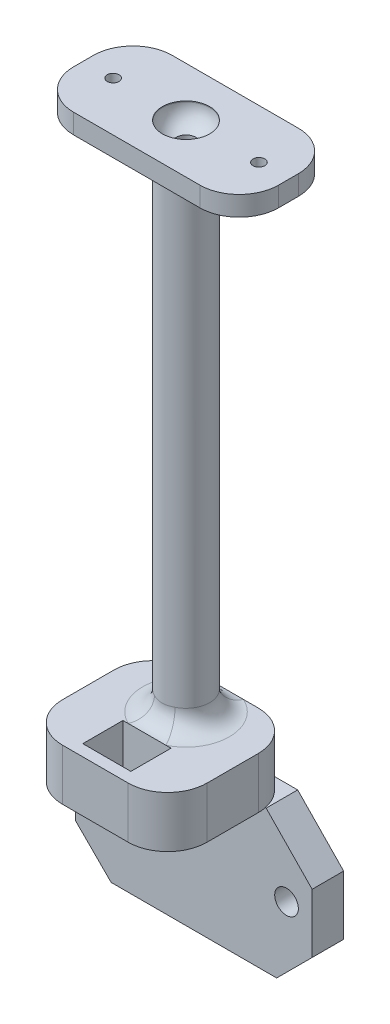
SolidWorks part; units mm, degrees
ref_plane "前视基准面" through (0, 0, 0) normal (0, 0, 1) x (1, 0, 0)
ref_plane "上视基准面" through (0, 0, 0) normal (0, 1, 0) x (1, 0, 0)
ref_plane "右视基准面" through (0, 0, 0) normal (1, 0, 0) x (0, 0, -1)
sketch "草图1" plane through (0, 0, 0) normal (0, 1, 0) x (1, 0, 0)
  line L0 (-32.0093, 0) -> (32.0093, 0) construction
  line L1 (-26, 12.5) -> (26, 12.5)
  line L2 (-26, 12.5) -> (-26, -12.5)
  line L3 (-26, -12.5) -> (26, -12.5)
  line L4 (26, 12.5) -> (26, -12.5)
  line L5 (-26, 12.5) -> (26, -12.5) construction
  line L6 (-26, -12.5) -> (26, 12.5) construction
  line L7 (0, 19.5739) -> (0, -19.5739) construction
  circle A0 centre (-18.5, 0) radius 1.5
  circle A1 centre (18.5, 0) radius 1.5
  point P0 (0, 0)
  point P9 (0, 0)
  point P12 (0, 0)
  dimension "D4" = 3
  dimension "D1" = 52
  dimension "D2" = 25
  dimension "D3" = 37
extrude "凸台-拉伸1" add sketch "草图1" along normal blind 5
sketch "草图2" plane through (0, 0, 0) normal (0, -1, 0) x (1, 0, 0)
  circle A0 centre (0, 0) radius 4
  circle A1 centre (0, 0) radius 2.5
  circle A2 centre (0, 0) radius 6
  dimension "D1" = 8
  dimension "D2" = 5
  dimension "D3" = 12
extrude "凸台-拉伸2" add sketch "草图2" along normal blind 125 contours A0 A1 region at (-3.8869, 0, 0)
fillet "圆角1" radius 10 4 edges at (26, 2.5, -12.5) (26, 2.5, 12.5) (-26, 2.5, -12.5) (-26, 2.5, 12.5)
extrude "凸台-拉伸4" add sketch "草图2<3>" along normal up to surface (125 mm away) contours A2 A0 region at (-5.8303, 0, 0) up to face at (0, -125, -2.5)
sketch "草图2<3>" plane through (0, 0, 0) normal (0, -1, 0) x (1, 0, 0) same geometry as "草图2"
fillet "圆角3" radius 5 1 edges at (0, 0, 6)
extrude "切除-拉伸1" cut sketch "草图2<4>" against normal blind 50 contours A2
sketch "草图2<4>" plane through (0, 0, 0) normal (0, -1, 0) x (1, 0, 0) same geometry as "草图2"
fillet "圆角4" radius 5 1 edges at (0, 0, -6)
sketch "草图3" plane through (0, 0, 0) normal (0, 0, 1) x (1, 0, 0)
  line L0 (0, -95.6549) -> (0, -154.3451) construction
  line L2 (18.3299, -125) -> (-18.3299, -125)
  line L3 (-18.3299, -125) -> (-18.3299, -138)
  line L4 (-18.3299, -138) -> (18.3299, -138)
  line L5 (18.3299, -138) -> (18.3299, -125)
  point P3 (0, -125)
  dimension "D1" = 13
extrude "凸台-拉伸5" add sketch "草图3" along normal blind 23 and the other way blind 10
sketch "草图4" plane through (0, -125, 0) normal (0, 1, 0) x (1, 0, 0)
  line L0 (0, 20.2764) -> (0, -20.2764) construction
  line L2 (-6.1, -20.1) -> (6.1, -20.1)
  line L3 (-6.1, -20.1) -> (-6.1, -9.9)
  line L4 (-6.1, -9.9) -> (6.1, -9.9)
  line L5 (6.1, -20.1) -> (6.1, -9.9)
  line L6 (-6.1, -20.1) -> (6.1, -9.9) construction
  line L7 (-6.1, -9.9) -> (6.1, -20.1) construction
  point P0 (0, -15)
  point P4 (0, 0)
  dimension "D1" = 10.2
  dimension "D2" = 12.2
  dimension "D3" = 15
extrude "切除-拉伸2" cut sketch "草图4" against normal blind 16
fillet "圆角5" radius 10 4 edges at (18.3299, -131.5, -10) (18.3299, -131.5, 23) (-18.3299, -131.5, -10) (-18.3299, -131.5, 23)
sketch "草图5" plane through (0, 0, -10) normal (0, 0, 1) x (1, 0, 0)
  line L4 (-18.3299, -138) -> (-30, -150)
  line L5 (-30, -150) -> (-30, -165)
  line L6 (-30, -165) -> (-21, -174)
  line L7 (-21, -174) -> (0, -174)
  line L8 (0, -138) -> (0, -174) construction
  line L9 (-8.3299, -138) -> (8.3299, -138) construction
  line L15 (18.3299, -138) -> (-18.3299, -138)
  line L16 (21, -174) -> (0, -174)
  line L17 (30, -165) -> (21, -174)
  line L18 (18.3299, -138) -> (30, -150)
  line L19 (30, -150) -> (30, -165)
  point P9 (-29.7731, -150)
  point P13 (-20.2959, -173)
  point P15 (0, -172.6024)
  point P17 (0.4688, -161.2707)
  dimension "D1" = 60
  dimension "D2" = 135
  dimension "D3" = 12
  dimension "D4" = 15
  dimension "D5" = 9
extrude "凸台-拉伸6" add sketch "草图5" along normal blind 8
sketch "草图6" plane through (0, -138, 0) normal (0, -1, 0) x (1, 0, 0)
  line L0 (-6.1, 20.1) -> (-6.1, 9.9) construction
  line L1 (6.1, 20.1) -> (-6.1, 20.1) construction
  line L2 (-6.1, 9.9) -> (6.1, 9.9) construction
  line L4 (6.1, 20.1) -> (-6.1, 20.1) construction
  line L6 (-6.1, 15) -> (6.1, 15) construction
  line L11 (6.1, 20.1) -> (6.1, 9.9) construction
  line L12 (-6.1, 9.9) -> (-6.1, 20.1) construction
  line L13 (1.4979, 15.0793) -> (-0.5742, 13.6143)
  line L14 (0, 20.1) -> (0, 4.7137) construction
  arc A0 (1.4979, 15.0793) -> (-0.5742, 13.6143) centre (0, 15) ccw
  dimension "D1" = 3
sketch "草图8" plane through (0, 0, -2) normal (0, 0, 1) x (1, 0, 0)
  line L0 (0, -138) -> (0, -174) construction
  line L1 (-8.3299, -138) -> (8.3299, -138) construction
  line L2 (-28.9111, -156) -> (28.9111, -156) construction
  line L4 (-21, -174) -> (21, -174) construction
  line L6 (-30, -150) -> (-30, -165) construction
  circle A0 centre (23.5, -156) radius 3
  circle A1 centre (-23.5, -156) radius 3
  point P8 (0, -156)
  point P9 (0, -175)
  point P14 (0, 0)
  point P15 (0, 0)
  point P16 (0, 0)
  point P18 (0, 0)
  point P21 (-30, -157.5)
  dimension "D1" = 6
  dimension "D2" = 47
  dimension "D3" = 1.5
sketch "草图9" plane through (0, -174, 0) normal (0, -1, 0) x (1, 0, 0)
  circle A0 centre (0, 15) radius 9
  circle A1 centre (0, 15) radius 2.5
  dimension "D1" = 18
  dimension "D2" = 5
sketch "草图10" plane through (0, -174, 0) normal (0, -1, 0) x (1, 0, 0)
  line L0 (21, -10) -> (21, -2)
  line L1 (-21, -10) -> (21, -10) construction
  line L2 (-21, -2) -> (21, -2) construction
  line L4 (21, -2) -> (-21, -2)
  line L5 (-21, -2) -> (21, -2) construction
  line L6 (-21, -2) -> (-21, -10)
  line L7 (-21, -2) -> (-21, -10) construction
  line L8 (-21, -10) -> (21, -10)
  line L9 (21, -2) -> (21, -10) construction
  point P16 (0, 0)
  point P17 (0, 0)
fillet "圆角9" radius 5 1 edges at (0, -125, -6)
extrude "凸台-拉伸7" add sketch "草图10" against normal blind 3
extrude "切除-拉伸5" cut sketch "草图8" against normal through all
